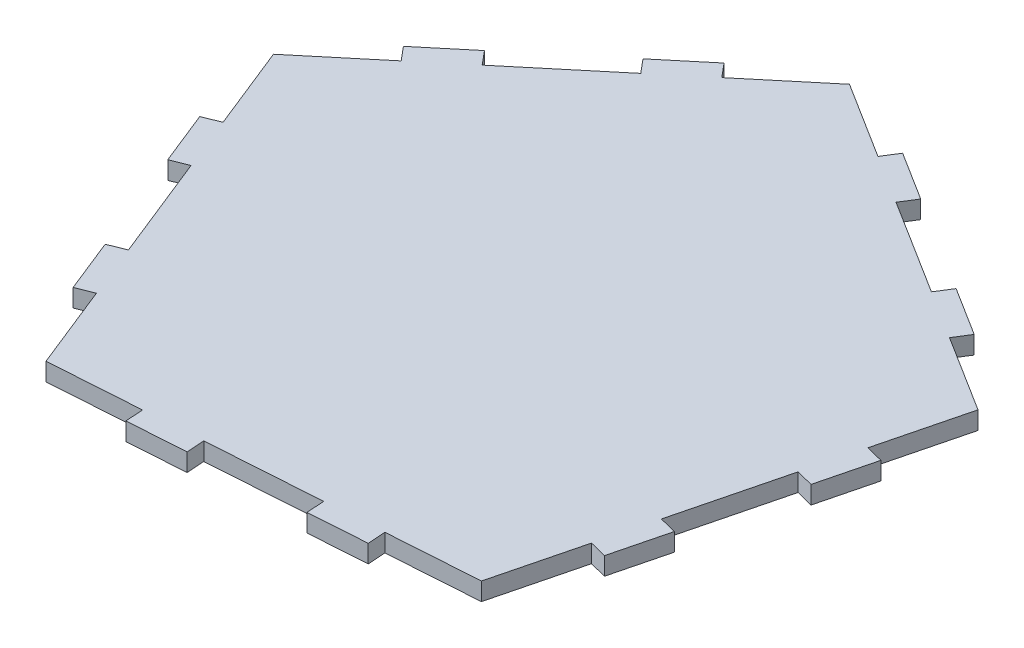
SolidWorks part; units mm, degrees
ref_plane "Front Plane" through (0, 0, 0) normal (0, 0, 1) x (1, 0, 0)
ref_plane "Top Plane" through (0, 0, 0) normal (0, 1, 0) x (1, 0, 0)
ref_plane "Right Plane" through (0, 0, 0) normal (1, 0, 0) x (0, 0, -1)
sketch "Sketch1" plane through (0, 0, 0) normal (0, 1, 0) x (1, 0, 0)
  line L1 (-63.7371, 16.0796) -> (-34.9884, -55.6487)
  line L2 (-34.9884, -55.6487) -> (42.1131, -50.4724)
  line L3 (42.1131, -50.4724) -> (61.0157, 24.4551)
  line L4 (61.0157, 24.4551) -> (-4.4033, 65.5865)
  line L5 (-4.4033, 65.5865) -> (-63.7371, 16.0796)
  circle A0 centre (0, 0) radius 53.18 construction
  dimension "D1" = 106.36
extrude "Boss-Extrude1" add sketch "Sketch1" along normal blind 3.18
sketch "Sketch2" plane through (0, 0, 0) normal (0, -1, 0) x (1, 0, 0)
  line L0 (-56.8852, 1.016) -> (-53.9335, -0.1671)
  line L1 (-56.8852, 1.016) -> (-53.0831, 10.5024)
  line L2 (-53.9335, -0.1671) -> (-50.1313, 9.3193)
  line L3 (-53.0831, 10.5024) -> (-50.1313, 9.3193)
  line L4 (-63.7371, -16.0796) -> (-34.9884, 55.6487) construction
  line L5 (-45.6425, 29.0668) -> (-41.8403, 38.5532)
  line L6 (-45.6425, 29.0668) -> (-42.6907, 27.8837)
  line L7 (-41.8403, 38.5532) -> (-38.8886, 37.3701)
  line L8 (-42.6907, 27.8837) -> (-38.8886, 37.3701)
  line L9 (-49.3628, 19.7846) -> (-19.2439, 7.7129) construction
  dimension "D1" = 3.18
  dimension "D2" = 10.22
  dimension "D3" = 10
extrude "Cut-Extrude1" [suppressed] cut sketch "Sketch2" against normal through all
ref_axis "Axis1" through (0, 3.339, 0) along (0, -1, 0)
pattern_circular "CirPattern1" [suppressed] count 5 over 360 about axis through (0, 3.339, 0) along (0, -1, 0) of bodies 102
sketch "Sketch3" plane through (0, 0, 0) normal (0, -1, 0) x (1, 0, 0)
  line L0 (-56.8852, 1.016) -> (-53.9335, -0.1671)
  line L1 (-56.8852, 1.016) -> (-53.0831, 10.5024)
  line L2 (-53.9335, -0.1671) -> (-50.1313, 9.3193)
  line L3 (-53.0831, 10.5024) -> (-50.1313, 9.3193)
  line L4 (-63.7371, -16.0796) -> (-34.9884, 55.6487) construction
  line L5 (-45.6425, 29.0668) -> (-42.6907, 27.8837)
  line L6 (-45.6425, 29.0668) -> (-41.8403, 38.5532)
  line L7 (-42.6907, 27.8837) -> (-38.8886, 37.3701)
  line L8 (-41.8403, 38.5532) -> (-38.8886, 37.3701)
  line L9 (0, 0) -> (-49.3628, 19.7846) construction
  line L10 (-65.563, -20.6353) -> (-62.6113, -21.8183)
  line L11 (-65.563, -20.6353) -> (-33.4497, 59.4878)
  line L12 (-62.6113, -21.8183) -> (-30.498, 58.3048)
  line L13 (-33.4497, 59.4878) -> (-30.498, 58.3048)
  line M14 (-63.7371, -16.0796) -> (-4.4033, -65.5865)
  line M17 (42.1131, 50.4724) -> (-34.9884, 55.6487)
  line M18 (-34.9884, 55.6487) -> (-63.7371, -16.0796)
  dimension "D1" = 10.22
  dimension "D2" = 10
  dimension "D3" = 3.18
  dimension "D4" = 3.18
extrude "Cut-Extrude2" cut sketch "Sketch3" against normal blind 10 contours L12 L0 M14 M18 | L12 L9 L11 L3 | L9 L12 L5 M18 | L8 L12 M17 M18 region at (-58.9188, 0, -8.3707) region at (-49.747, 0, 14.5519) region at (-46.0267, 0, 23.8342) region at (-36.8281, 0, 46.746)
pattern_circular "CirPattern2" count 5 over 360 about axis through (0, 3.339, 0) along (0, -1, 0) of "Cut-Extrude2"
equation "\"kerf\"= .22mm"
equation "\"tabWidth\"= 10 + \"kerf\" "
equation "\"tabSeperation\" = 10  "
equation "\"tabThickness\"= 3.18"
equation "\"D2@Sketch2\"=\"tabWidth\""
equation "\"D1@Sketch2\"=\"tabThickness\""
equation "\"D3@Sketch2\"=\"tabSeperation\""
equation "\"D1@Sketch3\"=\"tabWidth\""
equation "\"D2@Sketch3\"=\"tabSeperation\""
equation "\"D3@Sketch3\"=\"tabThickness\""
equation "\"D4@Sketch3\"=\"tabThickness\""
equation "\"tabLength\" = \"kerf\" + 12"
